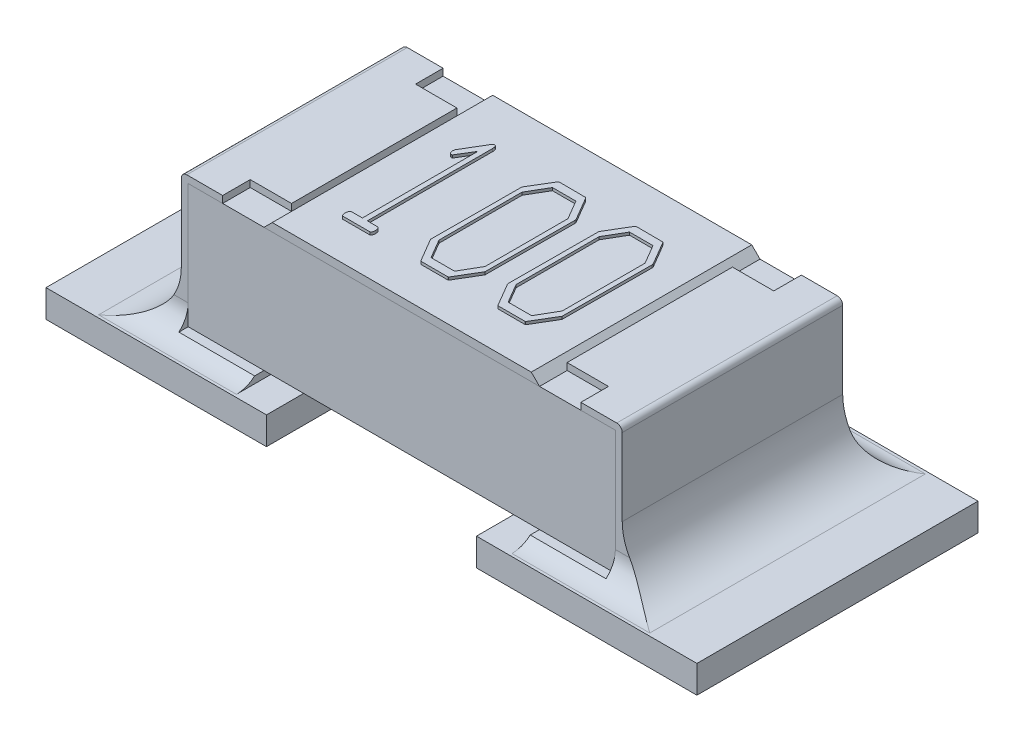
SolidWorks part; units mm, degrees
material "Ceramic Porcelain"
ref_plane "Front Plane" through (0, 0, 0) normal (0, 0, 1) x (1, 0, 0)
ref_plane "Top Plane" through (0, 0, 0) normal (0, 1, 0) x (1, 0, 0)
ref_plane "Right Plane" through (0, 0, 0) normal (1, 0, 0) x (0, 0, -1)
sketch "Sketch1" plane through (0, 0, 0) normal (1, 0, 0) x (0, 0, -1)
  line L0 (0, 55) -> (0, -55) construction
  line L1 (-0.4, 0.575) -> (0.4, 0.575)
  line L2 (-0.4, 0.575) -> (-0.4, 0.125)
  line L3 (-0.4, 0.125) -> (0.4, 0.125)
  line L4 (0.4, 0.575) -> (0.4, 0.125)
  line L5 (55, 0) -> (-55, 0) construction
  dimension "D1" = 0.8
  dimension "D2" = 0.4
  dimension "D3" = 0.45
  dimension "D4" = 0.125
extrude "Boss-Extrude1" add sketch "Sketch1" along normal mid plane 1.55
sketch "Sketch2" plane through (0, 0, 0) normal (0, 0, 1) x (1, 0, 0)
  line L0 (-0.5, 0.6) -> (-0.78, 0.6)
  line L1 (-0.8, 0.58) -> (-0.8, 0.1)
  line L2 (-0.8, 0.1) -> (-0.5, 0.1)
  line L3 (-0.5, 0.1) -> (-0.5, 0.125)
  line L4 (0.775, 0.125) -> (-0.775, 0.125) construction
  line L5 (-0.5, 0.125) -> (-0.775, 0.125)
  line L6 (-0.775, 0.125) -> (-0.775, 0.575)
  line L7 (-0.775, 0.575) -> (-0.5, 0.575)
  line L8 (0.775, 0.575) -> (-0.775, 0.575) construction
  line L9 (-0.5, 0.575) -> (-0.5, 0.6)
  line L11 (0.5, 0.575) -> (0.5, 0.6)
  line L12 (0.5, 0.6) -> (0.78, 0.6)
  line L13 (0.8, 0.58) -> (0.8, 0.1)
  line L14 (0.8, 0.1) -> (0.5, 0.1)
  line L15 (0.5, 0.1) -> (0.5, 0.125)
  line L16 (0.5, 0.125) -> (0.775, 0.125)
  line L17 (0.775, 0.125) -> (0.775, 0.575)
  line L18 (0.775, 0.575) -> (0.5, 0.575)
  arc A0 (0.78, 0.6) -> (0.8, 0.58) centre (0.78, 0.58) cw
  arc A1 (-0.78, 0.6) -> (-0.8, 0.58) centre (-0.78, 0.58) ccw
  point P28 (-0.8, 0.6)
  dimension "D6" = 0.02
  dimension "D1" = 0.025
  dimension "D2" = 0.025
  dimension "D3" = 0.025
  dimension "D4" = 0.3
  dimension "D5" = 0.3
extrude "Boss-Extrude2" add sketch "Sketch2" along normal mid plane 0.8 separate body
sketch "Sketch3" plane through (0, 0.6, 0) normal (0, 1, 0) x (1, 0, 0)
  line L0 (0.5, -0.4) -> (0.5, 0.4) construction
  line L1 (-0.5, 0.4) -> (-0.65, 0.4)
  line L2 (-0.5, 0.4) -> (-0.5, 0.3)
  line L3 (-0.5, 0.3) -> (-0.65, 0.3)
  line L4 (-0.65, 0.4) -> (-0.65, 0.3)
  line L5 (-0.5, -0.4) -> (-0.65, -0.4)
  line L6 (-0.5, -0.4) -> (-0.5, -0.3)
  line L7 (-0.5, -0.3) -> (-0.65, -0.3)
  line L8 (-0.65, -0.4) -> (-0.65, -0.3)
  line L9 (0.5, -0.4) -> (0.65, -0.4)
  line L10 (0.5, -0.4) -> (0.5, -0.3)
  line L11 (0.5, -0.3) -> (0.65, -0.3)
  line L12 (0.65, -0.4) -> (0.65, -0.3)
  line L13 (0.775, -0.4) -> (-0.775, -0.4) construction
  line L15 (0.5, 0.4) -> (0.65, 0.4)
  line L16 (0.5, 0.4) -> (0.5, 0.3)
  line L17 (0.5, 0.3) -> (0.65, 0.3)
  line L18 (0.65, 0.4) -> (0.65, 0.3)
  dimension "D1" = 0.15
  dimension "D2" = 0.1
extrude "Cut-Extrude1" cut sketch "Sketch3" against normal blind 0.025
sketch "Sketch4" plane through (0, 0, 0) normal (0, 0, 1) x (1, 0, 0)
  line L0 (-0.5, 0.575) -> (0.5, 0.575)
  line L1 (0.5, 0.575) -> (0.47, 0.605)
  line L2 (0.47, 0.605) -> (-0.47, 0.605)
  line L3 (-0.47, 0.605) -> (-0.5, 0.575)
  dimension "D1" = 45
  dimension "D2" = 45
  dimension "D3" = 0.03
extrude "Boss-Extrude3" add sketch "Sketch4" along normal mid plane 0.8 separate body
sketch "Sketch6" plane through (0, 0.605, 0) normal (0, 1, 0) x (1, 0, 0)
  line L0 (-0.4, -0.25) -> (0.4, -0.25) construction
  line L1 (0, -0.2777) -> (0, 0.2777) construction
  line L2 (-0.2777, 0) -> (0.2777, 0) construction
  line L3 (-0.47, -0.4) -> (-0.47, 0.4) construction
  line L4 (0.47, 0.4) -> (-0.47, 0.4) construction
  text T0 "100" font "SWMono" height 0.5
  dimension "D1" = 0.8
  dimension "D2" = 0.4
  dimension "D3" = 0.25
extrude "Boss-Extrude4" add sketch "Sketch6" along normal blind 0.01
sketch "Sketch7" plane through (0, 0, 0) normal (0, 1, 0) x (1, 0, 0)
  line L0 (0, -0.2833) -> (0, 0.2833) construction
  line L1 (-0.381, -0.51) -> (-1.181, -0.51)
  line L2 (-0.381, -0.51) -> (-0.381, 0.51)
  line L3 (-0.381, 0.51) -> (-1.181, 0.51)
  line L4 (-1.181, -0.51) -> (-1.181, 0.51)
  line L5 (0.381, -0.51) -> (1.181, -0.51)
  line L6 (0.381, -0.51) -> (0.381, 0.51)
  line L7 (0.381, 0.51) -> (1.181, 0.51)
  line L8 (1.181, -0.51) -> (1.181, 0.51)
  line L9 (-0.2833, 0) -> (0.2833, 0) construction
  dimension "D1" = 0.8
  dimension "D2" = 0.381
  dimension "D3" = 0.381
  dimension "D4" = 1.02
  dimension "D5" = 0.51
extrude "Boss-Extrude5" add sketch "Sketch7" along normal blind 0.1
fillet "Fillet3" radius 0.2 1 edges at (-0.8, 0.1, 0)
fillet "Fillet4" radius 0.2 1 edges at (0.8, 0.1, 0)
fillet "Fillet5" radius 0.1 2 edges at (0.75, 0.1, -0.4) (0.75, 0.1, 0.4)
fillet "Fillet6" radius 0.1 2 edges at (-0.75, 0.1, 0.4) (-0.75, 0.1, -0.4)
